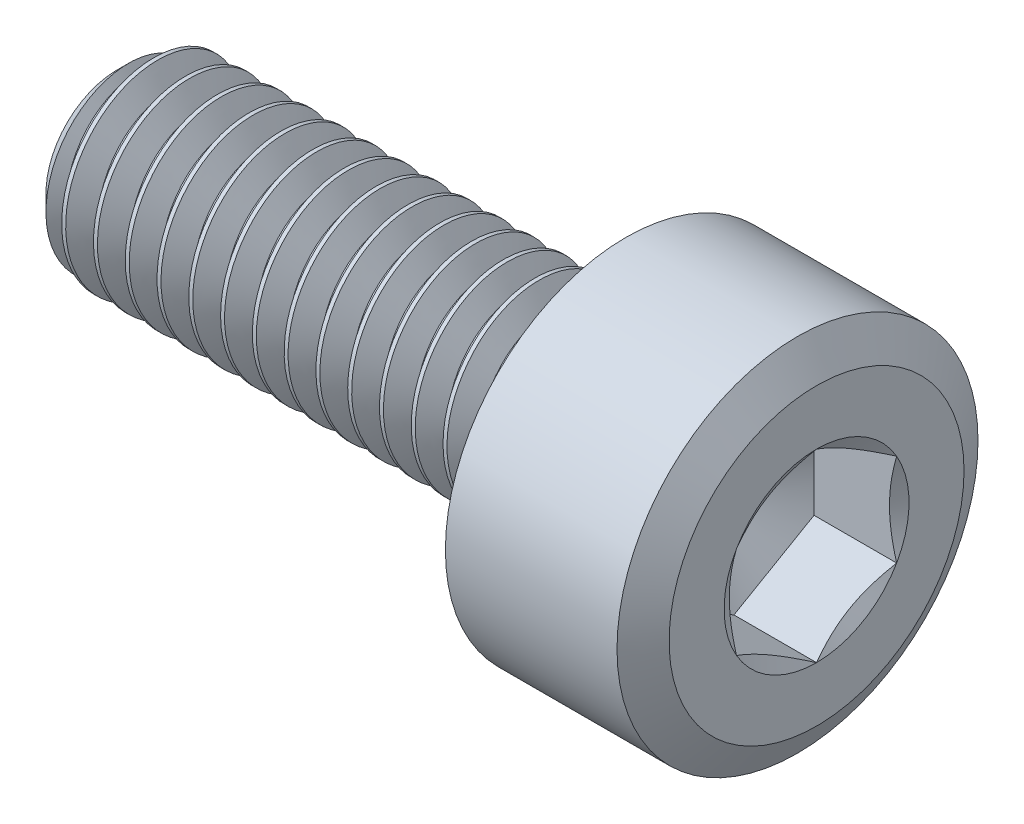
SolidWorks part; units mm, degrees
note: '?' marks a value the reader was unsure of.
ref_plane "Front Plane" through (0, 0, 0) normal (0, 0, 1) x (1, 0, 0)
ref_plane "Top Plane" through (0, 0, 0) normal (0, 1, 0) x (1, 0, 0)
ref_plane "Right Plane" through (0, 0, 0) normal (1, 0, 0) x (0, 0, -1)
sketch "Sketch1" plane through (0, 0, 0) normal (0, 0, 1) x (1, 0, 0)
  line L0 (5.5, 2.84) -> (5.5, -2.84) construction
  line L1 (5.5, 0) -> (-5.5, 0) construction
  line L2 (-5.5, 1.5) -> (-5.5, -1.5) construction
  line L3 (-5.5, 1.5) -> (2.5, 1.5) construction
  line L4 (5.5, 2.84) -> (2.5, 2.84) construction
  line L5 (5.5, 1.26) -> (4.2, 1.26) construction
  point P4 (5.5, 1.26)
  point P10 (-4.25, -1.5)
  point P12 (-5, 1.5)
  point P14 (2.5, 1.8)
  point P15 (3.65, 0)
  point P16 (5.2, 2.84)
  dimension "Length" = 8
  dimension "D | Screw Size Decimal Equivalent" = 3
  dimension "Thread Pitch" = 0.5
  dimension "S | Drive Size" = 2.52
  dimension "H | Head Diameter" = 5.68
  dimension "K | Head Height" = 3
  dimension "D1" = 1.25
  dimension "C" = 0.3
  dimension "F" = 3.6
  dimension "T" = 1.3
  dimension "W" = 1.15
sketch "Sketch2" plane through (0, 0, 0) normal (0, 0, 1) x (1, 0, 0)
  line L0 (-5.5, 1.125) -> (-5.5, 0)
  line L1 (-5.5, 0) -> (4.2, 0)
  line L3 (-5.125, 1.5) -> (2.2, 1.5)
  line L7 (-5.5, 1.125) -> (-5.125, 1.5)
  line L10 (-5.5, 1.5) -> (2.5, 1.5) construction
  line L11 (2.5, 2.84) -> (2.5, 1.8)
  line L12 (2.5, 2.84) -> (5.2, 2.84)
  line L13 (5.2, 2.84) -> (5.5, 2.3204)
  line L14 (5.5, 2.84) -> (5.5, -2.84) construction
  line L15 (5.5, 2.3204) -> (5.5, 1.26)
  line L16 (5.5, 1.26) -> (4.2, 1.26)
  line L19 (5.5, 0) -> (-5.5, 0) construction
  line L20 (4.2, 1.26) -> (4.2, 0)
  line L21 (5.5, 2.84) -> (2.5, 2.84) construction
  arc A0 (2.5, 1.8) -> (2.2, 1.5) centre (2.2, 1.8) cw
  dimension "D1" = 45
  dimension "D2" = 0.375
  dimension "D4" = 30
revolve "Revolve1" add sketch "Sketch2" angle 360 about L1
sketch "Sketch3" plane through (5.5, 0, 0) normal (1, 0, 0) x (0, 0, -1)
  line L0 (0, 1.5) -> (0, -1.5) construction
  line L1 (0, 1.4549) -> (-1.26, 0.7275)
  line L2 (-1.26, 0.7275) -> (-1.26, -0.7275)
  line L3 (-1.26, -0.7275) -> (0, -1.4549)
  line L4 (0, -1.4549) -> (1.26, -0.7275)
  line L5 (1.26, -0.7275) -> (1.26, 0.7275)
  line L6 (1.26, 0.7275) -> (0, 1.4549)
  circle A0 centre (0, 0) radius 1.26 construction
extrude "Cut-Extrude1" cut sketch "Sketch3" against normal up to vertex (1.3 mm away) up to point (4.2, 1.26, 0)
sketch "Sketch4" plane through (5.5, 0, 0) normal (1, 0, 0) x (0, 0, -1)
  line L0 (0, 1.5) -> (0, -1.5) construction
  circle A0 centre (0, 0) radius 1.4549
extrude "Cut-Extrude2" cut sketch "Sketch4" against normal through all draft 60
sketch "Sketch7" plane through (4.2, 0, 0) normal (1, 0, 0) x (0, 0, -1)
  line L0 (0, 1.5) -> (0, -1.5) construction
  circle A0 centre (0, 0) radius 1.4549
extrude "Cut-Extrude3" cut sketch "Sketch7" against normal up to vertex (0.55 mm away) draft 60 up to point (3.65, 0, 0)
ref_axis "Center Axis 1" through (5.5, 0, 0) along (-1, 0, 0)?
ref_plane "Plane1" through (2.2, 0, 0) normal (1, 0, 0) x (0, 0, -1)
split "Split1" trim tools "Plane1" bodies to split 111 resulting bodies 107 108
sketch "Sketch5" plane through (0, 0, 0) normal (0, 0, 1) x (1, 0, 0)
  line L0 (-5.9375, 1.5) -> (-5.5, 1.5) construction
  line L1 (-5.5, 1.5) -> (-5.7188, 1.1211) construction
  line L2 (-5.7188, 1.1211) -> (-5.9375, 1.5) construction
  line L3 (-5.9375, 1.5) -> (-5.9688, 1.5541) construction
  line L4 (-5.9688, 1.5541) -> (-5.4688, 1.5541) construction
  line L5 (-5.4688, 1.5541) -> (-5.5, 1.5) construction
  line L6 (-5.75, 1.1752) -> (-5.6875, 1.1752) construction
  line L7 (-5.7188, 1.1752) -> (-5.7188, 1.1211) construction
  line L8 (-5.7188, 1.5541) -> (-5.7188, 1.5) construction
  line L9 (-5.9531, 1.5271) -> (-5.4844, 1.5271)
  line L10 (-5.4844, 1.5271) -> (-5.6875, 1.1752)
  line L11 (-5.6875, 1.1752) -> (-5.75, 1.1752)
  line L12 (-5.75, 1.1752) -> (-5.9531, 1.5271)
  dimension "D1" = 0.5
  dimension "D2" = 0.0625
sketch "Sketch6" plane through (-5.5, 0, 0) normal (-1, 0, 0) x (0, 0, 1)
  line L0 (0, 1.5) -> (0, -1.5) construction
  circle A0 centre (0, 0) radius 1.5
curve "Helix/Spiral1" pitch 0.5 height 8.5 turns 17
sweep "Cut-Sweep1" cut profiles "Sketch5" path "Helix/Spiral1" align with end faces yes
combine bodies "Combine1" operation type add bodies to combine 109 107
equation "\"D1@Sketch1\"=\"Thread Pitch@Sketch1\"*2.5"
equation "\"D1\"= \"K | Head Height@Sketch1\" * .75"
equation "\"D1@Sketch5\"=\"Thread Pitch@Sketch1\""
equation "\"D2@Sketch5\"=\"Thread Pitch@Sketch1\"/8"
equation "\"D3@Helix/Spiral1\" = \"Length@Sketch1\" + \"Thread Pitch@Sketch1\""
equation "\"D4@Helix/Spiral1\"=\"Thread Pitch@Sketch1\""
equation "\"D2@Sketch2\"=\"Thread Pitch@Sketch1\"*.75"
